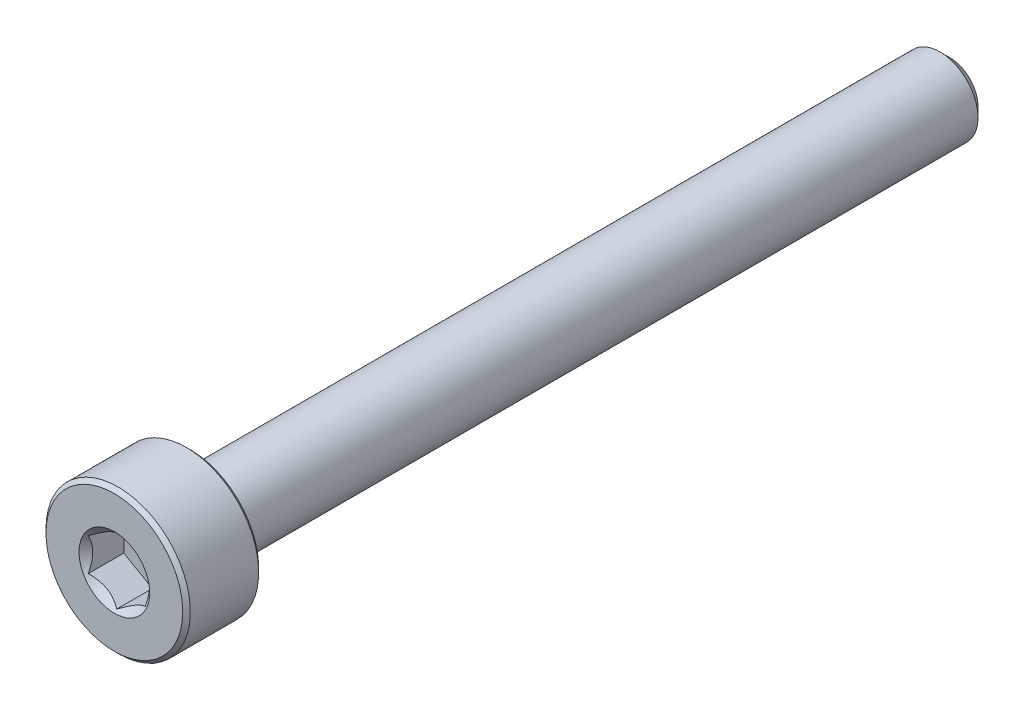
SolidWorks part; units mm, degrees
ref_plane "Front Plane" through (0, 0, 0) normal (0, 0, 1) x (1, 0, 0)
ref_plane "Top Plane" through (0, 0, 0) normal (0, 1, 0) x (1, 0, 0)
ref_plane "Right Plane" through (0, 0, 0) normal (1, 0, 0) x (0, 0, -1)
sketch "Sketch1" plane through (0, 0, 0) normal (1, 0, 0) x (0, 0, -1)
  line L0 (-11, 0) -> (11, 0) construction
  line L1 (11, 0) -> (11, 0.7402) construction
  line L2 (11, 0.7402) -> (10.7402, 1) construction
  line L3 (10.7402, 1) -> (10.7, 1) construction
  line L4 (10.7, 1) -> (-9, 1) construction
  line L5 (-9, 1) -> (-9, 1.9) construction
  line L6 (-9, 1.9) -> (-11, 1.9) construction
  line L7 (-11, 1.9) -> (-11, 0) construction
  line L8 (11, 0.7402) -> (11, 1) construction
  line L9 (10.975, 1.0433) -> (11.175, 0.6969) construction
  line L10 (11.175, 0.6969) -> (11.375, 1.0433) construction
  line L11 (11.375, 1.0433) -> (10.975, 1.0433) construction
  line L12 (11.175, 1.0433) -> (11.175, 1) construction
  line L13 (11.175, 0.6969) -> (11.175, 0.7402) construction
  line L14 (11.15, 0.7402) -> (11.2, 0.7402) construction
  line L15 (11, 1) -> (11.35, 1) construction
  line L16 (10.9875, 1.0217) -> (11.3625, 1.0217) construction
  line L17 (11, 0) -> (11, -1) construction
  line L18 (-9.1, 1.9) -> (-9, 1.8) construction
  line L19 (-10.9, 1.9) -> (-11, 1.8) construction
  line L20 (-9, 1) -> (-9, 0) construction
  line L21 (-9, 0.5) -> (-2.3333, 0.5) construction
  line L22 (-2.3333, 0.5) -> (4.3333, 0.5) construction
  line L23 (4.3333, 0.5) -> (11, 0.5) construction
  line L24 (-2.3333, 0.5) -> (-2.3333, 1) construction
  line L25 (-2.3333, 1) -> (-2.3333, 1.9) construction
  line L26 (4.3333, 0.5) -> (4.3333, 1.9) construction
  point P0 (-11, 0.75)
  point P3 (10, 1)
  point P4 (0, 0)
  point P18 (4.3333, 1)
  point P22 (11.175, 0.7402)
  point P24 (10.7, 1)
  point P25 (11.175, 1)
  point P28 (11.175, 1.0217)
  point P29 (10, -1)
  point P30 (-2.3333, 1)
  point P31 (-10, 1.9)
  point P37 (-9.35, 1.9)
  point P38 (-10.85, 1.9)
  point P45 (-2.3333, 0.5)
  point P46 (4.3333, 0.5)
  dimension "D2" = 0.05
  dimension "D7" = 0.1
  dimension "D8" = 0.1
  dimension "D9" = 0.1
  dimension "D10" = 0.05
  dimension "D11" = 0.25
  dimension "Drive Size" = 1.5
  dimension "Head Diameter" = 3.8
  dimension "Head Height" = 2
  dimension "Thread Pitch" = 0.4
  dimension "Thread Dia" = 2
  dimension "Length" = 20
  dimension "D12" = 0.3
  dimension "D4" = 1
  dimension "D3" = 45
sketch "Sketch2" plane through (0, 0, 0) normal (1, 0, 0) x (0, 0, -1)
  line L0 (-11, 0) -> (-11, 1.8)
  line L1 (-10.9, 1.9) -> (-9.1, 1.9)
  line L2 (-9, 1.8) -> (-9, 1.1)
  line L4 (10.7402, 1) -> (11, 0.7402)
  line L5 (11, 0.7402) -> (11, 0)
  line L6 (-9, 1.9) -> (-11, 1.9) construction
  line L7 (11, 0) -> (-11, 0)
  line L8 (-10.9, 1.9) -> (-11, 1.8) construction
  line L10 (-10.9, 1.9) -> (-11, 1.8)
  line L14 (-9.1, 1.9) -> (-9, 1.8) construction
  line L16 (-9.1, 1.9) -> (-9, 1.8)
  line L17 (-9, 1) -> (-9, 1.9) construction
  line L19 (-8.9, 1) -> (10.7402, 1)
  line L20 (10.7, 1) -> (-9, 1) construction
  arc A1 (-9, 1.1) -> (-8.9, 1) centre (-8.9, 1.1) ccw
  dimension "D3" = 0.1
revolve "Revolve1" add sketch "Sketch2" angle 360 about L7
sketch "Sketch3" plane through (0, 0, 11) normal (0, 0, 1) x (1, 0, 0)
  line L1 (0.75, -0.433) -> (0.75, 0.433)
  line L2 (0.75, 0.433) -> (0, 0.866)
  line L3 (0, 0.866) -> (-0.75, 0.433)
  line L4 (-0.75, 0.433) -> (-0.75, -0.433)
  line L5 (-0.75, -0.433) -> (0, -0.866)
  line L6 (0, -0.866) -> (0.75, -0.433)
  circle A0 centre (0, 0) radius 0.75 construction
  circle A1 centre (0, 0) radius 1.9 construction
  circle A2 centre (0, 0) radius 1.9 construction
  circle A3 centre (0, 0) radius 0.866 construction
  point P13 (0, 0)
  dimension "D1" = 1.7321
extrude "Cut-Extrude1" cut sketch "Sketch3" against normal offset from surface (1 mm away) 1 up to face at (-1.8, 0, 9)
sketch "Sketch4" plane through (0, 0, 11) normal (0, 0, 1) x (1, 0, 0)
  circle A0 centre (0, 0) radius 0.931
  dimension "D1" = 1.862
extrude "Cut-Extrude2" cut sketch "Sketch4" against normal up to vertex (1 mm away) draft 45 up to point (0, 1.9, 10)
sketch "Sketch11" plane through (0, 0, 0) normal (1, 0, 0) x (0, 0, -1)
  line L0 (-11, 0) -> (11, 0) construction
  line L1 (-11, 0) -> (11, 0) construction
  line L2 (-5.25, 0) -> (-5.25, 1) construction
  line L3 (10.7, 1) -> (-9, 1) construction
  line L4 (7.25, 0) -> (7.25, 1) construction
  line L6 (11, 0.7402) -> (11, 1) construction
  point P2 (-5.25, 0)
  point P3 (7.25, 0)
  dimension "D1" = 3.75
  dimension "D2" = 3.75
sketch "Sketch6" [suppressed] plane through (0, 0, -2.5) normal (0, 0, -1) x (-1, 0, 0)
  circle A0 centre (0, 0) radius 1
curve "Helix/Spiral1" [suppressed]
sketch "Sketch10" [suppressed] plane through (0, 0, 0) normal (1, 0, 0) x (0, 0, -1)
  line L0 (-0.4, -1.9) -> (-0.4, 1.9)
  line L5 (-2.5, 0) -> (2.5, 0) construction
  line L6 (-0.4, 1) -> (-0.4, -1) construction
  point P3 (-0.4, 0)
split "Split1" [suppressed] bodies to split 106
sketch "Sketch7" [suppressed] plane through (0, 0, 0) normal (1, 0, 0) x (0, 0, -1)
  line L0 (2.4875, 1.0217) -> (2.8625, 1.0217)
  line L1 (2.8625, 1.0217) -> (2.7, 0.7402)
  line L2 (2.7, 0.7402) -> (2.65, 0.7402)
  line L3 (2.65, 0.7402) -> (2.4875, 1.0217)
sweep "Cut-Sweep1" [suppressed] cut profiles "Sketch7" path "Helix/Spiral1"
sketch "Sketch8" [suppressed] plane through (0, 0, 0) normal (1, 0, 0) x (0, 0, -1)
  line L0 (-0.5, 0) -> (-0.5, 1)
  line L1 (-0.4, -1) -> (-0.4, 1) construction
  line L2 (-0.5, 1) -> (-0.4, 1)
  line L4 (-0.4, 1) -> (0.1774, 0)
  line L5 (0.1774, 0) -> (-0.5, 0)
  line L6 (2.2, 1) -> (-0.5, 1) construction
  line L7 (-2.5, 0) -> (2.5, 0) construction
  dimension "D1" = 60
revolve "Revolve2" [suppressed] add sketch "Sketch8" angle 360 about L5
equation "\"D2@Sketch1\" = \"Thread Pitch@Sketch1\" / 8"
equation "\"D4@Helix/Spiral1\" = \"Thread Pitch@Sketch1\""
equation "\"D7@Sketch1\" = \"Head Height@Sketch1\" * .05"
equation "\"D8@Sketch1\"=\"D7@Sketch1\""
equation "\"D9@Sketch1\"=\"D7@Sketch1\""
equation "\"D10@Sketch1\"=\"D7@Sketch1\"/2"
equation "\"D11@Sketch1\"=\"D10@Sketch1\"*5"
equation "\"D4@Sketch1\"=\"Thread Pitch@Sketch1\"*2.5"
equation "\"D12@Sketch1\"=\"Thread Pitch@Sketch1\"*.75"
equation "\"D3@Helix/Spiral1\"=\"Length@Sketch1\"+\"Thread Pitch@Sketch1\""
equation "\"D3@Sketch2\"=\"Thread Dia@Sketch1\"*0.05"
equation "\"D1@Sketch11\"=\"Length@Sketch1\"*0.1875"
equation "\"D2@Sketch11\"=\"D1@Sketch11\""
equation "\"D1@Sketch4\"=\"D1@Sketch3\"*1.075"
